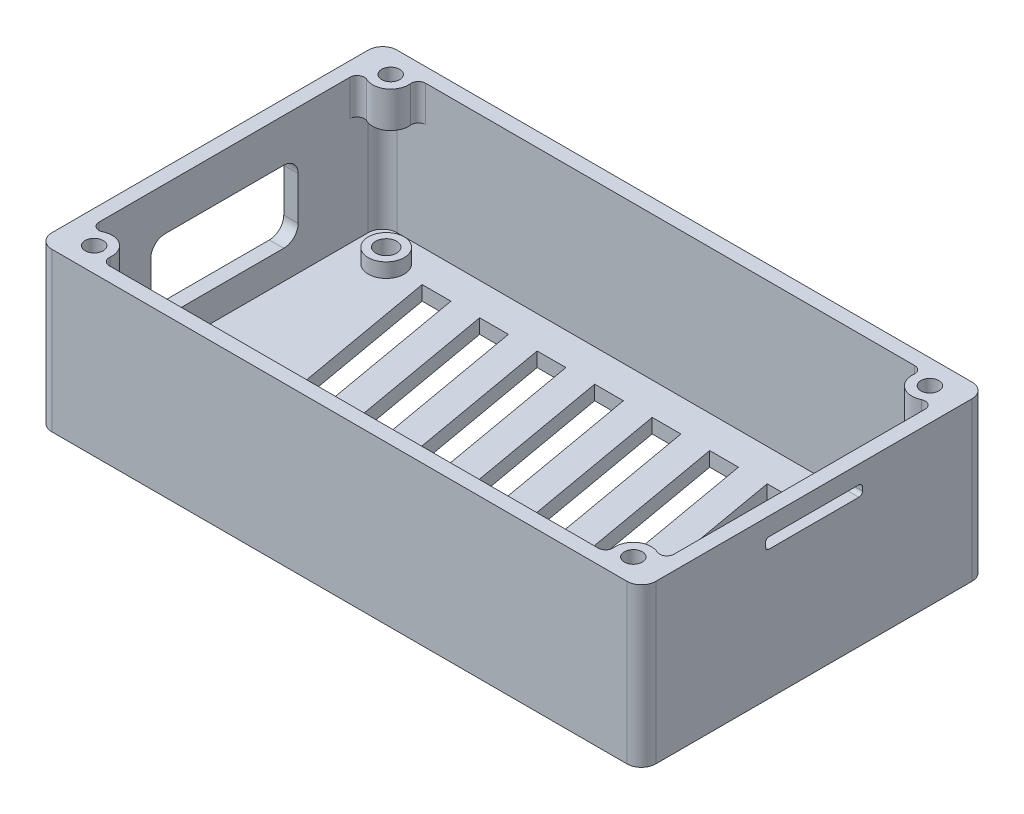
SolidWorks part; units mm, degrees
ref_plane "前视基准面" through (0, 0, 0) normal (0, 0, 1) x (1, 0, 0)
ref_plane "上视基准面" through (0, 0, 0) normal (0, 1, 0) x (1, 0, 0)
ref_plane "右视基准面" through (0, 0, 0) normal (1, 0, 0) x (0, 0, -1)
other "Configuration Table"
sketch "草图1" plane through (0, 0, 0) normal (0, 1, 0) x (1, 0, 0)
  line L0 (-40, 24) -> (40, 24)
  line L1 (-35, 17.5) -> (35, 17.5) construction
  line L2 (-35, 17.5) -> (-35, -17.5) construction
  line L3 (-35, -17.5) -> (35, -17.5) construction
  line L4 (35, 17.5) -> (35, -17.5) construction
  line L5 (-35, 17.5) -> (35, -17.5) construction
  line L6 (-35, -17.5) -> (35, 17.5) construction
  line L7 (-38, 22) -> (38, 22)
  line L8 (-40, 20) -> (-40, -20)
  line L9 (-38, -22) -> (38, -22)
  line L10 (40, 20) -> (40, -20)
  line L11 (-40, 22) -> (40, -22) construction
  line L12 (-40, -22) -> (40, 22) construction
  line L13 (42, 22) -> (42, -22)
  line L14 (-40, -24) -> (40, -24)
  line L15 (-42, 22) -> (-42, -22)
  line L16 (42, 24) -> (42, -24) construction
  line L17 (-42, -24) -> (42, -24) construction
  line L18 (-42, 24) -> (-42, -24) construction
  line L19 (-42, 24) -> (42, 24) construction
  line L20 (-40, 22) -> (40, 22) construction
  line L21 (40, 22) -> (40, -22) construction
  line L22 (-40, -22) -> (40, -22) construction
  line L23 (-40, 22) -> (-40, -22) construction
  circle A0 centre (-35, 17.5) radius 2.5
  circle A1 centre (35, 17.5) radius 2.5
  circle A2 centre (35, -17.5) radius 2.5
  circle A3 centre (-35, -17.5) radius 2.5
  arc A4 (42, -22) -> (40, -24) centre (40, -22) cw
  arc A5 (-40, -24) -> (-42, -22) centre (-40, -22) cw
  arc A6 (-42, 22) -> (-40, 24) centre (-40, 22) cw
  arc A7 (40, 24) -> (42, 22) centre (40, 22) cw
  arc A8 (38, 22) -> (40, 20) centre (38, 20) cw
  arc A9 (40, -20) -> (38, -22) centre (38, -20) cw
  arc A10 (-38, -22) -> (-40, -20) centre (-38, -20) cw
  arc A11 (-40, 20) -> (-38, 22) centre (-38, 20) cw
  circle A12 centre (-35, 17.5) radius 1.45
  circle A13 centre (35, 17.5) radius 1.45
  circle A14 centre (35, -17.5) radius 1.45
  circle A15 centre (-35, -17.5) radius 1.45
  point P0 (0, 0)
  point P10 (0, 0)
  dimension "D3" = 5
  dimension "D7" = 2
  dimension "D8" = 2.9
  dimension "D1" = 70
  dimension "D2" = 35
  dimension "D4" = 80
  dimension "D5" = 44
  dimension "D6" = 2
extrude "凸台-拉伸1" add sketch "草图1" against normal blind 2 contours L0 A7 L13 A4 L14 A5 L15 A6
extrude "凸台-拉伸3" add sketch "草图1<4>" along normal blind 20 contours L15 A5 L14 A4 L13 A7 L0 A6 | L8 A10 L9 A9 L10 A8 L7 A11
sketch "草图1<4>" plane through (0, 0, 0) normal (0, 1, 0) x (1, 0, 0) same geometry as "草图1"
extrude "凸台-拉伸4" add sketch "草图1<5>" along normal blind 2 contours A3 | A2 | A1 | A0 | A15 | A14 | A13 | A12
sketch "草图1<5>" plane through (0, 0, 0) normal (0, 1, 0) x (1, 0, 0) same geometry as "草图1"
sketch "草图2" plane through (0, -2, 0) normal (0, -1, 0) x (1, 0, 0)
  line L0 (-50.4953, 0) -> (50.4953, 0) construction
  line L7 (0, 30.7059) -> (0, -31.698) construction
  line L8 (-23.8286, 17.5) -> (-30, -17.5)
  line L9 (-30, 17.5) -> (30, 17.5)
  line L10 (-30, 17.5) -> (-30, -17.5)
  line L11 (-30, -17.5) -> (30, -17.5)
  line L12 (30, 17.5) -> (30, -17.5)
  line L13 (-30, 17.5) -> (30, -17.5) construction
  line L14 (-30, -17.5) -> (30, 17.5) construction
  line L15 (-27.8286, 17.5) -> (-30, 5.1851)
  line L16 (-19.8286, 17.5) -> (-26, -17.5)
  line L17 (-15.8286, 17.5) -> (-22, -17.5)
  line L18 (-11.8286, 17.5) -> (-18, -17.5)
  line L19 (-7.8286, 17.5) -> (-14, -17.5)
  line L20 (-3.8286, 17.5) -> (-10, -17.5)
  line L21 (0.1714, 17.5) -> (-6, -17.5)
  line L22 (4.1714, 17.5) -> (-2, -17.5)
  line L23 (8.1714, 17.5) -> (2, -17.5)
  line L24 (12.1714, 17.5) -> (6, -17.5)
  line L25 (16.1714, 17.5) -> (10, -17.5)
  line L26 (20.1714, 17.5) -> (14, -17.5)
  line L27 (24.1714, 17.5) -> (18, -17.5)
  line L28 (28.1714, 17.5) -> (22, -17.5)
  line L29 (30, 5.1851) -> (26, -17.5)
  line L37 (33.0857, 0) -> (30, -17.5) [skipped]
  point P0 (0, 0)
  point P3 (0, 0)
  point P6 (0, -0.496)
  dimension "D1" = 60
  dimension "D2" = 35
  dimension "D3" = 80
  dimension "D4" = 4
  dimension "D5" = 16
extrude "切除-拉伸2" cut sketch "草图2" against normal blind 2 contours L12 L29 L11 | L28 L9 L27 L11 | L26 L9 L25 L11 | L24 L9 L23 L11 | L22 L9 L21 L11 | L20 L9 L19 L11 | L18 L9 L17 L11 | L16 L9 L8 L11 | L15 L9 L10 region at (-24.9143, -2, 0) region at (-29.2762, -2, 13.395) region at (-16.9143, -2, 0) region at (-8.9143, -2, 0) region at (-0.9143, -2, 0) region at (7.0857, -2, 0) region at (15.0857, -2, 0) region at (23.0857, -2, 0) region at (28.6667, -2, -9.9383)
sketch "草图3" plane through (-40, 0, 0) normal (1, 0, 0) x (0, 0, -1)
  line L0 (-10.25, 0) -> (10.25, 0) construction
  line L1 (20, 0) -> (-20, 0) construction
  line L2 (0, 0) -> (0, 26.674) construction
  line L3 (-10.25, 6) -> (-10.25, 12)
  line L4 (10.25, 6) -> (10.25, 12)
  line L5 (-8.25, 4) -> (8.25, 4)
  line L6 (-8.25, 14) -> (8.25, 14)
  arc A0 (8.25, 14) -> (10.25, 12) centre (8.25, 12) cw
  arc A1 (10.25, 6) -> (8.25, 4) centre (8.25, 6) cw
  arc A2 (-8.25, 4) -> (-10.25, 6) centre (-8.25, 6) cw
  arc A3 (-10.25, 12) -> (-8.25, 14) centre (-8.25, 12) cw
  point P0 (0, 0)
  point P7 (0, 0)
  point P14 (0, 4)
  point P17 (0, 14)
  dimension "D5" = 2
  dimension "D1" = 20.5
  dimension "D2" = 4
  dimension "D3" = 10
  dimension "D4" = 20.5
extrude "切除-拉伸3" cut sketch "草图3" against normal blind 2 contours L6 A0 L4 A1 L5 A2 L3 A3
sketch "草图4" plane through (40, 0, 0) normal (-1, 0, 0) x (0, 0, 1)
  line L0 (0, 0) -> (0, 27.4858) construction
  line L1 (-6.25, 16) -> (6.25, 16)
  line L2 (-15, 2) -> (-20, 2) construction
  line L3 (-6.25, 17.5) -> (6.25, 17.5)
  line L4 (-6.75, 17) -> (-6.75, 16.5)
  line L5 (6.75, 17) -> (6.75, 16.5)
  arc A0 (6.25, 17.5) -> (6.75, 17) centre (6.25, 17) cw
  arc A1 (6.75, 16.5) -> (6.25, 16) centre (6.25, 16.5) cw
  arc A2 (-6.25, 16) -> (-6.75, 16.5) centre (-6.25, 16.5) cw
  arc A3 (-6.75, 17) -> (-6.25, 17.5) centre (-6.25, 17) cw
  point P6 (0, 16)
  point P11 (0, 17.5)
  point P13 (6.75, 17.5)
  point P20 (-6.75, 17.5)
  dimension "D4" = 0.5
  dimension "D1" = 14
  dimension "D2" = 1.5
  dimension "D3" = 13.5
extrude "切除-拉伸4" cut sketch "草图4" against normal blind 10
ref_plane "基准面1" through (-40, 20, -20) normal (0, 0, 1) x (1, 0, 0)
sketch "草图6" plane through (0, 20, 0) normal (0, 1, 0) x (1, 0, 0)
  circle A1 centre (37.5, 20.625) radius 2.5
  circle A2 centre (37.5, 20.625) radius 2.5
  circle A3 centre (37.5, -20.625) radius 2.5
  circle A4 centre (37.5, -20.625) radius 2.5
  circle A5 centre (-37.5, -20.625) radius 2.5
  circle A6 centre (-37.5, -20.625) radius 2.5
  circle A7 centre (-37.5, 20.625) radius 2.5
  circle A8 centre (-37.5, 20.625) radius 2.5
  circle A9 centre (37.5, 20.625) radius 1.25
  circle A10 centre (37.5, 20.625) radius 1.25
  circle A11 centre (37.5, -20.625) radius 1.25
  circle A12 centre (37.5, -20.625) radius 1.25
  circle A13 centre (-37.5, -20.625) radius 1.25
  circle A14 centre (-37.5, -20.625) radius 1.25
  circle A15 centre (-37.5, 20.625) radius 1.25
  circle A16 centre (-37.5, 20.625) radius 1.25
  dimension "D1" = 0
  dimension "D2" = 0
  dimension "D3" = 0
  dimension "D4" = 0
  dimension "D5" = 0
  dimension "D6" = 0
  dimension "D7" = 0
  dimension "D8" = 0
extrude "凸台-拉伸5" add sketch "草图6" against normal blind 5
fillet "圆角1" radius 1 8 edges at (-39.9781, 17.5, 20.295) (-35.4121, 17.5, 22) (-39.9781, 17.5, -20.295) (-35.4121, 17.5, -22) (35.4121, 17.5, -22) (39.9781, 17.5, -20.295) (39.9781, 17.5, 20.295) (35.4121, 17.5, 22)
